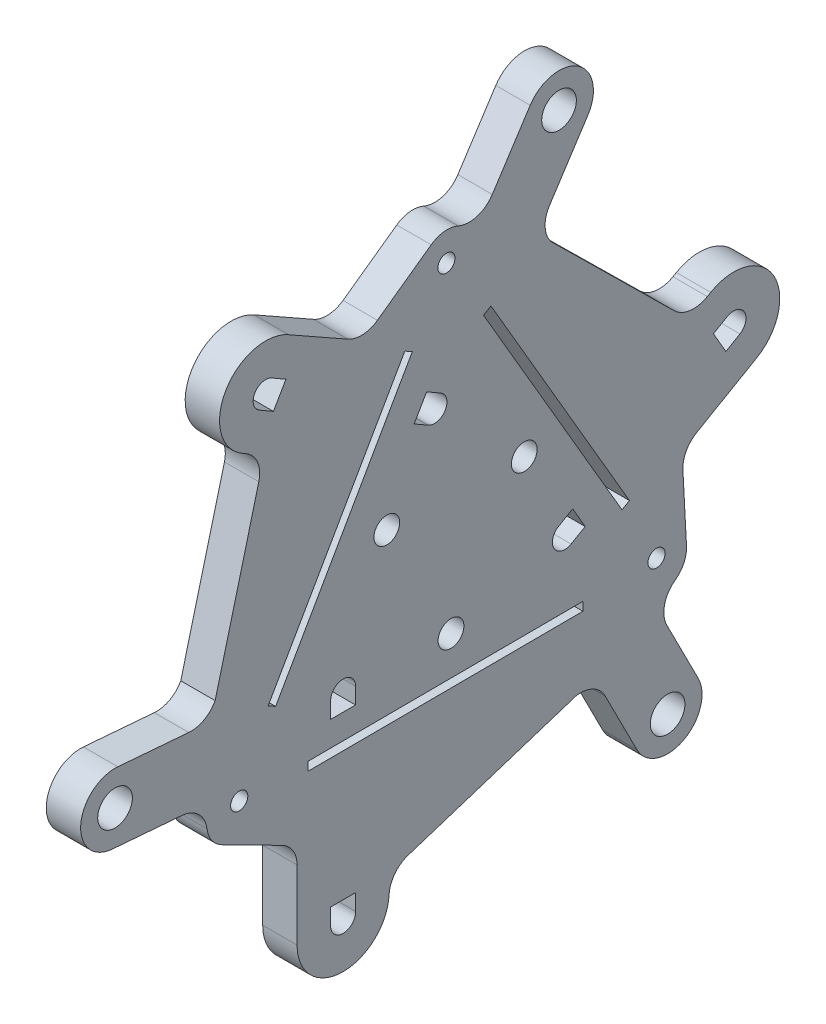
SolidWorks part; units mm, degrees
material "Polyethylene Cross-Linked"
ref_plane "Front Plane" through (0, 0, 0) normal (0, 0, 1) x (1, 0, 0)
ref_plane "Top Plane" through (0, 0, 0) normal (0, 1, 0) x (1, 0, 0)
ref_plane "Right Plane" through (0, 0, 0) normal (1, 0, 0) x (0, 0, -1)
sketch "Sketch1" plane through (0, 0, 0) normal (1, 0, 0) x (0, 0, -1)
  line L0 (0, 0) -> (44.5, 0)
  line L1 (0, 0) -> (22.25, 38.5381)
  line L2 (22.25, 38.5381) -> (44.5, 0)
  line L3 (0.8998, 11.0585) -> (12.8998, 31.8431)
  line L4 (12.8998, 31.8431) -> (22.25, 38.5381)
  line L5 (0.8998, 11.0585) -> (0, 0)
  line L6 (0, 0) -> (10.25, -5.2142)
  line L7 (10.25, -5.2142) -> (34.25, -5.2142)
  line L8 (34.25, -5.2142) -> (44.5, 0)
  line L9 (44.5, 0) -> (43.8906, 11.4838)
  line L10 (43.8906, 11.4838) -> (31.8906, 32.2685)
  line L11 (31.8906, 32.2685) -> (22.25, 38.5381)
  line L12 (22.25, 38.5381) -> (22.25, 0) construction
  line L13 (44.5, 0) -> (11.125, 19.2691) construction
  line L14 (0, 0) -> (33.375, 19.2691) construction
  point P17 (22.25, 12.846)
  dimension "D2" = 44.5
  dimension "D4" = 60
  dimension "D5" = 60
  dimension "D6" = 24
  dimension "D7" = 11.5
  dimension "D8" = 4.75
extrude "Boss-Extrude1" add sketch "Sketch1" along normal blind 3.175 contours L10 L11 L2 L9 | L2 L1 L0 | L3 L5 L1 L4 | L7 L8 L0 L6 region at (0, 12.846, -22.25) region at (0, 20.2511, -9.2231) region at (0, -2.347, -22.25) region at (0, 20.4426, -35.4076)
sketch "Sketch7" plane through (0, 0, 0) normal (-1, 0, 0) x (0, 0, 1)
  circle A0 centre (-22.25, 35.3631) radius 0.7937
  circle A2 centre (-3.1199, 1.927) radius 0.7937
  circle A3 centre (-41.6415, 2.0779) radius 0.7938
  point P8 (-22.3734, 12.7748)
  dimension "D1" = 1.5875
  dimension "D2" = 0
  dimension "D3" = 3.175
  dimension "D4" = 3
extrude "Cut-Extrude6" cut sketch "Sketch7" against normal through all
sketch "Sketch8" plane through (0, 0, 0) normal (-1, 0, 0) x (0, 0, 1)
  line L0 (-43.8906, 11.4838) -> (-31.8906, 32.2685)
  line L1 (-43.8906, 11.4838) -> (-48.015, 13.8651)
  line L2 (-31.8906, 32.2685) -> (-36.015, 34.6497)
  line L3 (-48.015, 13.8651) -> (-36.015, 34.6497)
  line L8 (-10.25, -5.2142) -> (-34.25, -5.2142)
  line L9 (-10.25, -5.2142) -> (-10.25, -9.9767)
  line L10 (-10.25, -9.9767) -> (-34.25, -9.9767)
  line L11 (-34.25, -5.2142) -> (-34.25, -9.9767)
  line L13 (-8.485, 34.6497) -> (3.515, 13.8651) [skipped]
  line L14 (-0.6094, 11.4838) -> (3.515, 13.8651) [skipped]
  line L15 (-12.6094, 32.2685) -> (-8.485, 34.6497) [skipped]
  line L16 (-12.6094, 32.2685) -> (-0.6094, 11.4838) [skipped]
  line L17 (-12.8998, 31.8431) -> (-0.8998, 11.0585)
  line L18 (-12.8998, 31.8431) -> (-8.7753, 34.2243)
  line L19 (-0.8998, 11.0585) -> (3.2247, 13.4397)
  line L20 (-8.7753, 34.2243) -> (3.2247, 13.4397)
  line L21 (-0.8998, 11.0585) -> (-12.8998, 31.8431) construction
  point P0 (-50.9991, 31.3695)
  point P13 (-22.25, 12.846)
  dimension "D1" = 4.7625
  dimension "D3" = 4.7625
  dimension "D2" = 3
extrude "Boss-Extrude2" add sketch "Sketch8" against normal blind 3.175
sketch "Sketch9" plane through (3.175, 0, 0) normal (1, 0, 0) x (0, 0, -1)
  line L0 (3.4327, 29.558) -> (5.4191, 28.4112)
  line L1 (-3.2247, 13.4397) -> (8.7753, 34.2243) construction
  line L2 (5.4191, 28.4112) -> (8.7753, 34.2243)
  line L3 (8.7753, 34.2243) -> (12.8998, 31.8431)
  line L4 (12.8998, 31.8431) -> (14.5626, 33.0337)
  line L5 (12.8998, 31.8431) -> (22.25, 38.5381) construction
  line L6 (7.6827, 36.9192) -> (14.5626, 33.0337)
  line L7 (8.4625, -12.2704) -> (8.4625, -4.3049)
  line L8 (0, 0) -> (10.25, -5.2142) construction
  line L9 (8.4625, -4.3049) -> (10.25, -5.2142)
  line L10 (10.25, -5.2142) -> (10.25, -9.9767)
  line L15 (16.9625, -10.7704) -> (16.9625, -12.2704)
  line L16 (11.5625, -12.2704) -> (11.5625, -10.7704)
  line L17 (11.5625, -10.7704) -> (13.8625, -10.7703)
  line L18 (13.8625, -10.7703) -> (13.8625, -12.2704)
  line L19 (4.9826, 32.2427) -> (6.2818, 31.4927)
  line L20 (6.2818, 31.4927) -> (7.4317, 33.4845)
  line L21 (7.4317, 33.4845) -> (6.1326, 34.2346)
  line L22 (46.6452, 20.8252) -> (44.6588, 19.6783)
  line L23 (36.015, 34.6497) -> (48.015, 13.8651) construction
  line L24 (50.8952, 13.4639) -> (43.9969, 9.4812)
  line L25 (44.5, 0) -> (43.8906, 11.4838) construction
  line L26 (37.9049, 5.9639) -> (48.2972, 11.9639) construction
  line L27 (43.9969, 9.4812) -> (43.8906, 11.4838)
  line L28 (43.8906, 11.4838) -> (48.015, 13.8651)
  line L29 (48.015, 13.8651) -> (44.6588, 19.6783)
  line L30 (48.1952, 18.1405) -> (46.8961, 17.3904)
  line L31 (46.8961, 17.3904) -> (48.0462, 15.3982)
  line L32 (46.4641, 18.1387) -> (48.478, 14.6501) construction
  line L33 (48.0462, 15.3982) -> (49.3452, 16.1486)
  line L35 (16.9625, -10.7704) -> (20.6064, -10.7704)
  line L36 (10.25, -9.4292) -> (10.25, -9.9767)
  line L37 (20.6064, -10.7704) -> (20.6064, -9.9767)
  line L38 (34.25, -9.9767) -> (10.25, -9.9767) construction
  line L39 (20.6064, -9.9767) -> (10.25, -9.9767)
  arc A0 (3.4327, 29.558) -> (7.6827, 36.9192) centre (5.5577, 33.2386) cw
  arc A1 (16.9625, -12.2704) -> (8.4625, -12.2704) centre (12.7125, -12.2704) cw
  arc A2 (11.5625, -12.2704) -> (13.8625, -12.2704) centre (12.7125, -12.3069) ccw
  arc A3 (4.9826, 32.2427) -> (6.1326, 34.2346) centre (5.5576, 33.2386) cw
  arc A4 (46.6452, 20.8252) -> (50.8952, 13.4639) centre (48.7702, 17.1445) cw
  arc A5 (48.1952, 18.1405) -> (49.3452, 16.1486) centre (48.7544, 17.1354) cw
  point P16 (7.6827, 36.9192)
extrude "Boss-Extrude3" add sketch "Sketch9" against normal blind 3.175 contours L6 L4 L3 L2 L0 A0 | L29 L22 A4 L24 L27 L28 | L39 L37 L35 L15 A1 L7 L9 L10 | L33 A5 L30 L31 | L21 A3 L19 L20 | A2 L18 L17 L16
sketch "Sketch12" plane through (3.175, 0, 0) normal (1, 0, 0) x (0, 0, -1)
  line L0 (33.7568, 7.1486) -> (35.0559, 7.8987)
  line L1 (35.0559, 7.8987) -> (33.9059, 9.8905)
  line L2 (33.9059, 9.8905) -> (32.6068, 9.1405)
  line L3 (21.7211, 25.2346) -> (20.422, 25.9846)
  line L4 (20.422, 25.9846) -> (19.272, 23.9928)
  line L5 (20.8539, 26.7331) -> (18.84, 23.2445) construction
  line L6 (19.272, 23.9928) -> (20.5711, 23.2427)
  line L7 (13.8625, 5.7296) -> (13.8625, 4.2295)
  line L8 (13.8625, 4.2295) -> (11.5625, 4.2295)
  line L9 (11.5625, 4.2295) -> (11.5625, 5.7296)
  arc A0 (32.6068, 9.1405) -> (33.7568, 7.1486) centre (33.1818, 8.1446) ccw
  arc A1 (11.5625, 5.7296) -> (13.8625, 5.7296) centre (12.7125, 5.7296) cw
  arc A2 (20.5711, 23.2427) -> (21.7211, 25.2346) centre (21.1461, 24.2386) ccw
extrude "Cut-Extrude8" cut sketch "Sketch12" against normal blind 3.175
sketch "Sketch10" plane through (3.175, 0, 0) normal (1, 0, 0) x (0, 0, -1)
  line L0 (31.8906, 32.2685) -> (44.6588, 19.6783)
  line L1 (44.6588, 19.6783) -> (36.015, 34.6497)
  line L2 (36.015, 34.6497) -> (31.8906, 32.2685)
  line L3 (5.4191, 28.4112) -> (0.8998, 11.0585)
  line L4 (0.8998, 11.0585) -> (-3.2247, 13.4397)
  line L5 (-3.2247, 13.4397) -> (5.4191, 28.4112)
  line L11 (16.9625, -10.7704) -> (34.25, -5.2142)
  line L12 (34.25, -5.2142) -> (34.25, -11.4141)
  line L13 (34.25, -11.4141) -> (16.9625, -10.7704)
extrude "Cut-Extrude7" cut sketch "Sketch10" against normal blind 3.175
fillet "Fillet1" radius 2.54 1 edges at (1.5875, -10.7704, -16.9625)
fillet "Fillet2" radius 2.54 8 edges at (1.5875, 9.4812, -43.9969) (1.5875, 0, -44.5) (1.5875, 19.6783, -44.6588) (1.5875, 38.5381, -22.25) (1.5875, 33.0337, -14.5626) (1.5875, 28.4112, -5.4191) (1.5875, 0, 0) (1.5875, -4.3049, -8.4625)
sketch "Sketch13" plane through (0, 0, 0) normal (-1, 0, 0) x (0, 0, 1)
  line L0 (-34.25, -5.2142) -> (-18.716, -10.2068) construction
  line L1 (-29.4368, 16.2939) -> (-22.6725, 5.5452)
  line L2 (-22.6725, 5.5452) -> (-16.746, 16.7775)
  line L3 (-16.746, 16.7775) -> (-29.4368, 16.2939)
  circle A0 centre (-22.9518, 12.8722) radius 3.6662 construction
  circle A2 centre (-22.6725, 5.5452) radius 1.1906
  circle A3 centre (-29.4368, 16.2939) radius 1.1906
  circle A4 centre (-16.746, 16.7775) radius 1.1906
  point P8 (-22.9518, 12.8722)
  dimension "D2" = 2.3813
  dimension "D1" = 12.7
  dimension "D3" = 80
extrude "Cut-Extrude9" cut sketch "Sketch13" against normal blind 3.175 contours L2 A4 L3 | L3 A4 L2 | A2 | A3 region at (0, 16.8583, -16.6177) region at (0, 16.3738, -17.3875)
sketch "Sketch14" plane through (0, 0, 0) normal (-1, 0, 0) x (0, 0, 1)
  line L0 (-41.6415, 2.0779) -> (-3.1199, 1.927)
  line L1 (-3.1199, 1.927) -> (-22.25, 35.3631)
  line L2 (-22.25, 35.3631) -> (-41.6415, 2.0779)
  line L3 (-6.4828, 7.8048) -> (-19.0966, 29.8515)
  line L4 (-6.4828, 7.8048) -> (-5.7939, 8.199)
  line L5 (-19.0966, 29.8515) -> (-18.4076, 30.2457)
  line L6 (-5.7939, 8.199) -> (-18.4076, 30.2457)
  line L7 (-34.8486, 2.0212) -> (-9.4488, 1.9217)
  line L8 (-34.8486, 2.0212) -> (-34.8517, 1.2274)
  line L9 (-34.8517, 1.2274) -> (-9.4519, 1.1279)
  line L10 (-9.4488, 1.9217) -> (-9.4519, 1.1279)
  line L11 (-25.6745, 29.4785) -> (-38.4606, 7.5314)
  line L12 (-25.6745, 29.4785) -> (-26.3604, 29.8781)
  line L13 (-26.3604, 29.8781) -> (-39.1465, 7.9309)
  line L14 (-38.4606, 7.5314) -> (-39.1465, 7.9309)
  dimension "D1" = 25.4
  dimension "D2" = 6.35
  dimension "D3" = 0.7937
  dimension "D4" = 3
extrude "Cut-Extrude10" cut sketch "Sketch14" against normal blind 3.175 contours L10 L7 L8 L9 | L14 L2 L12 L13 | L4 L6 L5 L1 | L13 L14 L11 L12 region at (0, 18.7055, -32.4119) region at (0, 19.0252, -12.4452) region at (0, 1.5746, -22.1503)
sketch "Sketch17" plane through (0, 0, 0) normal (-1, 0, 0) x (0, 0, 1)
  line L0 (-35.809, -4.4211) -> (-39.8397, -12.3448)
  line L1 (-34.25, -5.2142) -> (-43.0277, -0.749) construction
  line L2 (-41.4687, -1.542) -> (-45.4995, -9.4657)
  line L3 (-35.809, -4.4211) -> (-41.4687, -1.542)
  line L4 (-0.2615, 3.2135) -> (8.5992, 3.9345)
  line L5 (-0.8998, 11.0585) -> (-0.1381, 1.6976) construction
  line L6 (-0.7764, 9.5426) -> (8.0843, 10.2636)
  line L7 (-0.2615, 3.2135) -> (-0.7764, 9.5426)
  line L8 (-25.1355, 36.6616) -> (-29.9822, 44.1142)
  line L9 (-31.8906, 32.2685) -> (-23.7036, 37.5928) construction
  line L10 (-30.4588, 33.1996) -> (-35.3055, 40.6522)
  line L11 (-25.1355, 36.6616) -> (-30.4588, 33.1996)
  arc A0 (-39.8397, -12.3448) -> (-45.4995, -9.4657) centre (-42.6696, -10.9053) cw
  circle A1 centre (-42.6696, -10.9053) radius 1.6
  arc A2 (8.5992, 3.9345) -> (8.0843, 10.2636) centre (8.3418, 7.099) ccw
  circle A3 centre (8.3418, 7.099) radius 1.6
  arc A4 (-29.9822, 44.1142) -> (-35.3055, 40.6522) centre (-32.6439, 42.3832) ccw
  circle A5 centre (-32.6439, 42.3832) radius 1.6
  point P8 (-38.6388, -2.9816)
  point P16 (-0.519, 6.3781)
  point P27 (-27.7971, 34.9306)
  dimension "D2" = 3.175
  dimension "D3" = 3.2
  dimension "D1" = 8.89
extrude "Boss-Extrude5" add sketch "Sketch17" against normal up to surface (3.175 mm away) up to face at (3.175, 19.0252, -12.4452)
fillet "Fillet4" radius 2.54 6 edges at (1.5875, 36.6616, -25.1355) (1.5875, 33.1996, -30.4588) (1.5875, -1.542, -41.4687) (1.5875, -4.4211, -35.809) (1.5875, 9.5426, -0.7764) (1.5875, 3.2135, -0.2615)
equation "\"HOLE_SIZE\"= 3.2mm"
